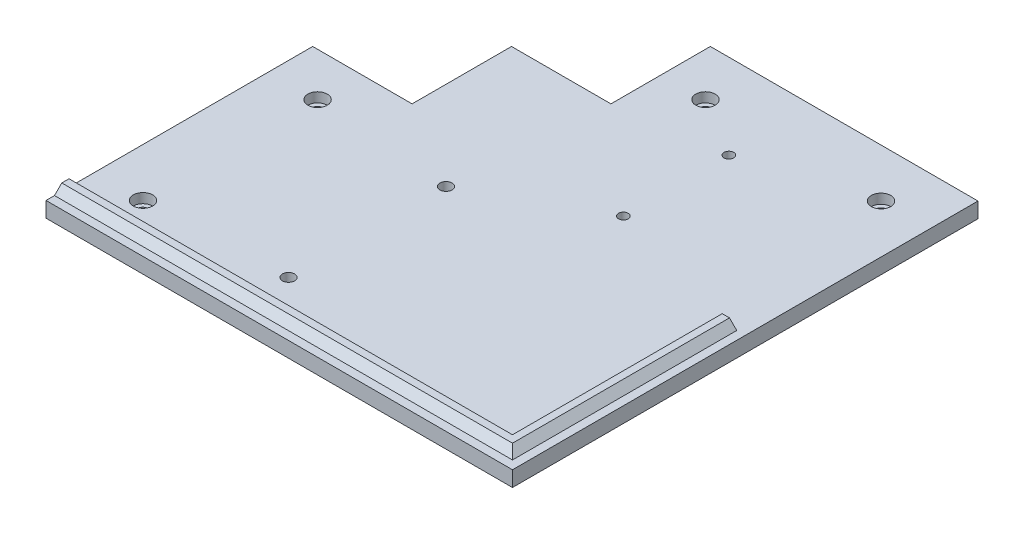
SolidWorks part; units mm, degrees
ref_plane "Front Plane" through (0, 0, 0) normal (0, 0, 1) x (1, 0, 0)
ref_plane "Top Plane" through (0, 0, 0) normal (0, 1, 0) x (1, 0, 0)
ref_plane "Right Plane" through (0, 0, 0) normal (1, 0, 0) x (0, 0, -1)
sketch "Sketch1" plane through (0, 0, 0) normal (0, 1, 0) x (1, 0, 0)
  line L1 (-96.2, 96) -> (96.2, 96)
  line L2 (-96.2, 96) -> (-96.2, -96)
  line L3 (-96.2, -96) -> (96.2, -96)
  line L4 (96.2, 96) -> (96.2, -96)
  line L5 (-96.2, 96) -> (96.2, -96) construction
  line L6 (-96.2, -96) -> (96.2, 96) construction
  point P0 (0, 0)
  dimension "D1" = 192
  dimension "D2" = 192.4
extrude "Boss-Extrude1" add sketch "Sketch1" along normal blind 6.35
sketch "Sketch2" plane through (0, 6.35, 0) normal (0, 1, 0) x (1, 0, 0)
  line L1 (-96.2, 96) -> (-55.2, 96)
  line L2 (-96.2, 96) -> (-96.2, 55)
  line L3 (-96.2, 55) -> (-55.2, 55) construction
  line L4 (-55.2, 96) -> (-55.2, 55) construction
  line L5 (-96.2, 55) -> (-55.2, 55)
  line L6 (-96.2, 55) -> (-96.2, 14)
  line L7 (-96.2, 14) -> (-55.2, 14)
  line L8 (-55.2, 55) -> (-55.2, 14)
  line L9 (-55.2, 96) -> (-14.2, 96)
  line L10 (-55.2, 96) -> (-55.2, 55)
  line L11 (-55.2, 55) -> (-14.2, 55)
  line L12 (-14.2, 96) -> (-14.2, 55)
  line M14 (96.2, 96) -> (-96.2, 96)
  line M15 (-96.2, 96) -> (-96.2, -96)
  dimension "D1" = 41
extrude "Cut-Extrude1" cut sketch "Sketch2" against normal up to next contours L8 L5 L7 M15 | L10 L5 M14 M15 | L12 L10 L11 M14 region at (-75.7, 6.35, -75.5) region at (-34.7, 6.35, -75.5) region at (-75.7, 6.35, -34.5)
sketch "Sketch3" plane through (0, 6.35, 0) normal (0, 1, 0) x (1, 0, 0)
  line L0 (-96.2, 76) -> (96.2, 76) construction
  line L1 (-96.2, 96) -> (-56.2, 96) construction
  line L2 (-96.2, 96) -> (-96.2, -96) construction
  line L3 (-96.2, -96) -> (-56.2, -96) construction
  line L4 (96.2, 96) -> (-96.2, 96)
  line L5 (96.2, -96) -> (96.2, 96)
  line L6 (-96.2, -96) -> (96.2, -96)
  line L7 (-96.2, 96) -> (-96.2, -96)
  line L8 (96.2, 96) -> (-96.2, 96) construction
  line L9 (96.2, -96) -> (96.2, 96) construction
  line L10 (-96.2, -96) -> (96.2, -96) construction
  line L11 (-96.2, 96) -> (-96.2, -96) construction
  line L12 (-56.2, 96) -> (-56.2, -96) construction
  line L13 (-96.2, 96) -> (96.2, 96) construction
  line L14 (-96.2, 96) -> (-96.2, 56) construction
  line L15 (-96.2, 56) -> (96.2, 56) construction
  line L16 (96.2, 96) -> (96.2, 56) construction
  line L17 (-76.2, 96) -> (-76.2, -96) construction
  point P20 (-76.2, -4)
  point P22 (-76.2, -76)
  point P24 (3.8, 76)
  point P26 (76.2, 76)
  dimension "D2" = 40
  dimension "D3" = 40
  dimension "D4" = 20
  dimension "D5" = 60
  dimension "D6" = 60
  dimension "D7" = 20
  dimension "D8" = 20
  dimension "D1" = 0
hole_wizard "CBORE for M4 SHCS1" positions "Sketch3" profile "Sketch4" counterbore size "M4" standard "ANSI Metric" end condition up to next
sketch "Sketch4" plane through (76.2, 6.35, -76) normal (1, 0, 0) x (0, 0, 1)
  line L0 (0, 0) -> (0, 6.35)
  line L1 (0, 6.35) -> (2.25, 6.35)
  line L3 (2.25, 6.35) -> (2.25, 4)
  line L4 (2.25, 4) -> (4, 4)
  line L5 (4, 4) -> (4, 0)
  line L7 (4, 0) -> (0, 0)
  line L11 (0, -6.35) -> (0, 107.95) construction
  dimension "Thru Hole Dia." = 4.5
  dimension "Thru Hole Depth" = 6.35
  dimension "C'Bore Dia." = 8
  dimension "C'Bore Depth" = 4
mirror "Mirror1" [suppressed] of bodies 105
delete or keep bodies "Body-Delete/Keep 1" [suppressed] type delete bodies bodies 105
mirror "Mirror2" [suppressed] of bodies 108
delete or keep bodies "Body-Delete/Keep 2" [suppressed] type delete bodies bodies 108
sketch "Sketch5" plane through (0, 6.35, 0) normal (0, 1, 0) x (1, 0, 0)
  line L0 (-18.7, -8.525) -> (-18.7, -73.475) construction
  line L1 (-56.2, -4.375) -> (18.8, -4.375) construction
  line L2 (-56.2, -4.375) -> (-56.2, -77.625) construction
  line L3 (-56.2, -77.625) -> (18.8, -77.625) construction
  line L4 (18.8, -4.375) -> (18.8, -77.625) construction
  line L5 (-96.2, -41) -> (96.2, -41) construction
  line L6 (-96.2, 14) -> (-96.2, -96) construction
  line L7 (96.2, -96) -> (96.2, 96) construction
  line L8 (-56.2, -41) -> (18.8, -41) construction
  circle A0 centre (-18.7, -8.525) radius 2.5
  circle A1 centre (-18.7, -73.475) radius 2.5
  point P12 (-18.7, -41)
  point P15 (-18.7, -41)
  dimension "D4" = 5
  dimension "D1" = 73.25
  dimension "D2" = 75
  dimension "D3" = 40
  dimension "D5" = 64.95
extrude "Cut-Extrude2" cut sketch "Sketch5" against normal blind 6
sketch "Sketch6" plane through (0, 0.35, 0) normal (0, 1, 0) x (1, 0, 0)
  circle A0 centre (-18.7, -8.525) radius 2.25
  circle A1 centre (-18.7, -73.475) radius 2.25
  dimension "D1" = 4.5
extrude "Cut-Extrude3" cut sketch "Sketch6" against normal up to next
sketch "Sketch7" plane through (0, 6.35, 0) normal (0, 1, 0) x (1, 0, 0)
  line L0 (96.2, -96) -> (96.2, 96) construction
  line L1 (28.45, 61) -> (163.95, 61) construction
  line L2 (28.45, 61) -> (28.45, 17.5) construction
  line L3 (28.45, 17.5) -> (163.95, 17.5) construction
  line L4 (163.95, 61) -> (163.95, 17.5) construction
  line L5 (28.45, 61) -> (163.95, 17.5) construction
  line L6 (28.45, 17.5) -> (163.95, 61) construction
  line L7 (96.2, 96) -> (-14.2, 96) construction
  circle A0 centre (28.45, 61) radius 1.75
  circle A1 centre (28.45, 17.5) radius 1.75
  point P0 (96.2, 39.25)
  dimension "D4" = 3.5
  dimension "D1" = 43.5
  dimension "D2" = 135.5
  dimension "D3" = 35
extrude "Cut-Extrude4" cut sketch "Sketch7" against normal up to next
sketch "Sketch8" plane through (0, 6.35, 0) normal (0, 1, 0) x (1, 0, 0)
  circle A0 centre (28.45, 61) radius 2
  circle A1 centre (28.45, 17.5) radius 2
  dimension "D1" = 4
extrude "Cut-Extrude5" cut sketch "Sketch8" against normal blind 5
sketch "Sketch9" plane through (0, 6.35, 0) normal (0, 1, 0) x (1, 0, 0)
  line L2 (0, 0) -> (96.2, 0) construction
  line L3 (96.2, -96) -> (96.2, 96) construction
  line L4 (-96.2, -88) -> (88.2, -88)
  line L5 (88.2, -88) -> (88.2, 96)
  line L6 (-96.2, -88) -> (88.2, -88)
  line L7 (88.2, -88) -> (88.2, 0)
  dimension "D1" = 8
extrude "Extrude-Thin1" add sketch "Sketch9" along normal blind 3 thin thin type mid plane wall 3
chamfer "Chamfer1" distance 3 angle 45 4 edges at (-4.75, 6.35, 86.5) (86.7, 6.35, 43.25) (-3.25, 6.35, 89.5) (89.7, 6.35, 44.75)
mirror "Mirror3" [suppressed] of bodies 113
delete or keep bodies "Body-Delete/Keep 4" [suppressed] type delete bodies bodies 113
equation "\"D2@Sketch1\"=384.8/2"
